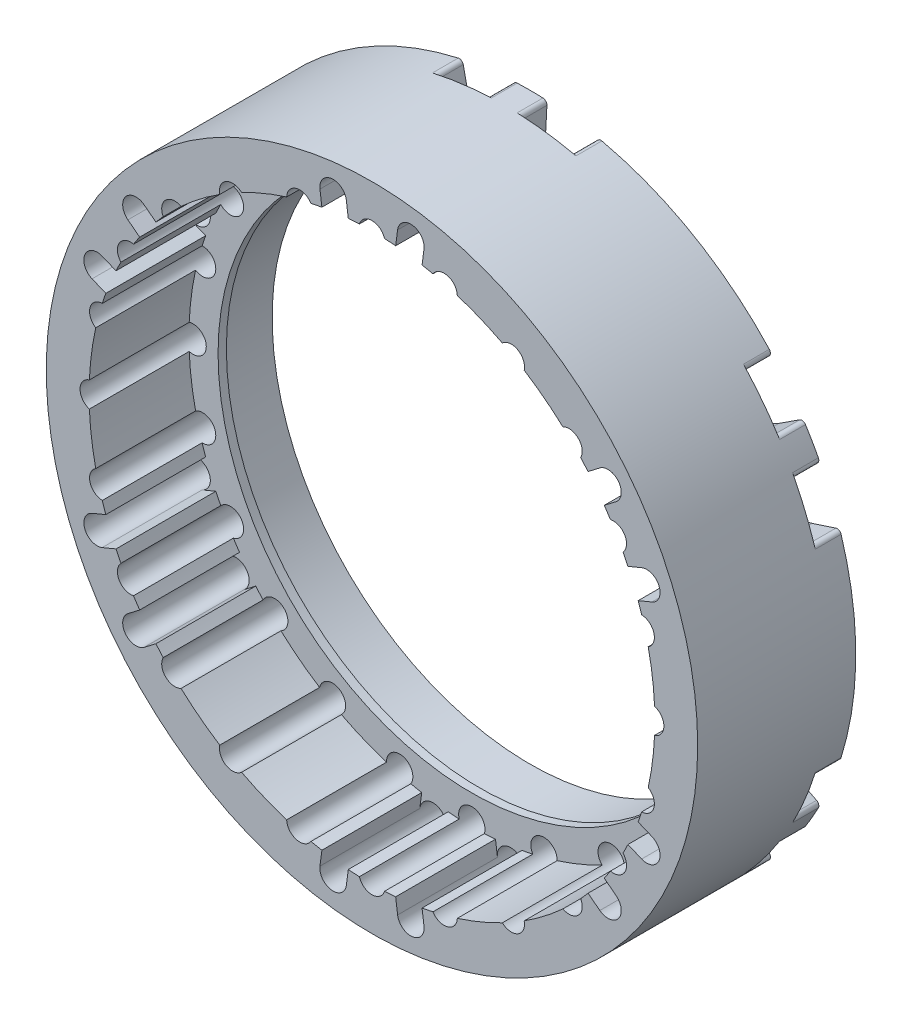
SolidWorks part; units mm, degrees
material "ABS"
ref_plane "Front Plane" through (0, 0, 0) normal (0, 0, 1) x (1, 0, 0)
ref_plane "Top Plane" through (0, 0, 0) normal (0, 1, 0) x (1, 0, 0)
ref_plane "Right Plane" through (0, 0, 0) normal (1, 0, 0) x (0, 0, -1)
sketch "CYC Master Sketch" plane through (0, 0, 0) normal (0, 0, 1) x (1, 0, 0)
  circle A0 centre (0, 0) radius 39.15
  circle A2 centre (0, 0) radius 33.5 construction
  circle A3 centre (-33.5, 0) radius 1.585
  circle A4 centre (-32.3585, 8.6704) radius 1.585
  circle A5 centre (-29.0119, 16.75) radius 1.585
  circle A6 centre (-23.6881, 23.6881) radius 1.585
  circle A7 centre (-16.75, 29.0119) radius 1.585
  circle A8 centre (-8.6704, 32.3585) radius 1.585
  circle A9 centre (0, 33.5) radius 1.585
  circle A10 centre (8.6704, 32.3585) radius 1.585
  circle A11 centre (16.75, 29.0119) radius 1.585
  circle A12 centre (23.6881, 23.6881) radius 1.585
  circle A13 centre (29.0119, 16.75) radius 1.585
  circle A14 centre (32.3585, 8.6704) radius 1.585
  circle A15 centre (33.5, 0) radius 1.585
  circle A16 centre (32.3585, -8.6704) radius 1.585
  circle A17 centre (29.0119, -16.75) radius 1.585
  circle A18 centre (23.6881, -23.6881) radius 1.585
  circle A19 centre (16.75, -29.0119) radius 1.585
  circle A20 centre (8.6704, -32.3585) radius 1.585
  circle A21 centre (0, -33.5) radius 1.585
  circle A22 centre (-8.6704, -32.3585) radius 1.585
  circle A23 centre (0, 0) radius 34
  circle A24 centre (-16.75, -29.0119) radius 1.585
  circle A25 centre (-23.6881, -23.6881) radius 1.585
  circle A26 centre (-29.0119, -16.75) radius 1.585
  circle A27 centre (-32.3585, -8.6704) radius 1.585
  circle A28 centre (0, 0) radius 31 construction
  circle A29 centre (0, 0) radius 24.975 construction
  circle A30 centre (0, 0) radius 35.75 construction
  circle A31 centre (4.6663, -35.4442) radius 1.6
  circle A32 centre (-4.6663, -35.4442) radius 1.6
  circle A33 centre (-28.3624, -21.7632) radius 1.6
  circle A34 centre (-33.0287, -13.6809) radius 1.6
  circle A35 centre (-33.0287, 13.6809) radius 1.6
  circle A36 centre (-28.3624, 21.7632) radius 1.6
  circle A37 centre (-4.6663, 35.4442) radius 1.6
  circle A38 centre (4.6663, 35.4442) radius 1.6
  circle A39 centre (28.3624, 21.7632) radius 1.6
  circle A40 centre (33.0287, 13.6809) radius 1.6
  circle A41 centre (33.0287, -13.6809) radius 1.6
  circle A42 centre (28.3624, -21.7632) radius 1.6
  point P47 (0, 0)
  point P72 (0, 0)
extrude "Gearbox Wall" add sketch "CYC Master Sketch" along normal blind 19 contours A0 A23 A13 A14 A15 A16 A17 A18 A19 A20 A21 A22 A3 A4 A5 A6 A7 A8 A9 A10 A11 A12 region at (-38.0427, 0, 0)
extrude "Gearbox Bottom" add sketch "CYC Master Sketch<3>" along normal blind 7 contours A21 A23 | A23 A20 | A20 A23 | A23 A19 | A19 A23 | A23 A18 | A18 A23 | A23 A17 | A17 A23 | A23 A16 | A16 A23 | A23 A15 | A15 A23 | A23 A14 | A14 A23 | A23 A13 | A13 A23 | A23 A12 | A12 A23 | A23 A11 | A11 A23 | A23 A10 | A10 A23 | A23 A9 | A9 A23 | A23 A8 | A8 A23 | A23 A7 | A7 A23 | A23 A6 | A6 A23 | A23 A5 | A5 A23 | A23 A4 | A4 A23 | A23 A3 | A3 A23 | A23 A22 | A22 A23 | A13 A23 A12 A11 A10 A9 A8 A7 A6 A5 A4 A3 A22 A21 A20 A19 A18 A17 A16 A15 A14 | A24 | A25 | A26 | A27 | A21 region at (-33.0823, 0, 0) region at (0, 0, 0) region at (-34.4435, 0, 0) region at (-31.9551, 8.5623, 0) region at (-33.2699, 8.9146, 0) region at (-28.6502, 16.5412, 0) region at (-29.829, 17.2218, 0) region at (-23.3928, 23.3928, 0) region at (-24.3553, 24.3553, 0) region at (-16.5412, 28.6502, 0) region at (-17.2218, 29.829, 0) region at (-8.5623, 31.9551, 0) region at (-8.9146, 33.2699, 0) region at (-8.9146, -33.2699, 0) region at (-8.5623, -31.9551, 0) region at (0, 33.0823, 0) region at (0, 34.4435, 0) region at (0, -33.0823, 0) region at (8.5623, 31.9551, 0) region at (8.9146, 33.2699, 0) region at (8.9146, -33.2699, 0) region at (8.5623, -31.9551, 0) region at (16.5412, 28.6502, 0) region at (17.2218, 29.829, 0) region at (17.2218, -29.829, 0) region at (16.5412, -28.6502, 0) region at (23.3928, 23.3928, 0) region at (24.3553, 24.3553, 0) region at (24.3553, -24.3553, 0) region at (23.3928, -23.3928, 0) region at (28.6502, 16.5412, 0) region at (29.829, 17.2218, 0) region at (29.829, -17.2218, 0) region at (28.6502, -16.5412, 0) region at (31.9551, 8.5623, 0) region at (33.2699, 8.9146, 0) region at (33.2699, -8.9146, 0) region at (31.9551, -8.5623, 0) region at (33.0823, 0, 0) region at (34.4435, 0, 0)
sketch "CYC Master Sketch<3>" plane through (0, 0, 0) normal (0, 0, 1) x (1, 0, 0) same geometry as "CYC Master Sketch"
extrude "Pin Cut" cut sketch "CYC Master Sketch<2>" against normal blind 4 from surface contours A23 A7 | A7 A23 | A23 A6 | A6 A23 | A23 A5 | A5 A23 | A23 A4 | A4 A23 | A23 A3 | A3 A23 | A23 A22 | A22 A23 | A23 A21 | A21 A23 | A23 A20 | A20 A23 | A23 A19 | A19 A23 | A23 A18 | A18 A23 | A23 A17 | A17 A23 | A16 A23 | A23 A16 | A15 A23 | A23 A15 | A23 A14 | A14 A23 | A23 A13 | A13 A23 | A23 A12 | A12 A23 | A23 A11 | A11 A23 | A10 A23 | A23 A9 | A9 A23 | A23 A8 | A8 A23 | A23 A10 | A23 A24 | A23 A24 | A23 A25 | A23 A25 | A23 A26 | A23 A26 | A23 A27 | A23 A27 region at (-33.0823, 0, 0) region at (-34.4435, 0, 0) region at (-31.9551, 8.5623, 0) region at (-33.2699, 8.9146, 0) region at (-31.9551, -8.5623, 0) region at (-33.2699, -8.9146, 0) region at (-28.6502, 16.5412, 0) region at (-29.829, 17.2218, 0) region at (-28.6502, -16.5412, 0) region at (-29.829, -17.2218, 0) region at (-23.3928, 23.3928, 0) region at (-24.3553, 24.3553, 0) region at (-23.3928, -23.3928, 0) region at (-24.3553, -24.3553, 0) region at (-16.5412, 28.6502, 0) region at (-17.2218, 29.829, 0) region at (-16.5412, -28.6502, 0) region at (-17.2218, -29.829, 0) region at (-8.5623, 31.9551, 0) region at (-8.9146, 33.2699, 0) region at (-8.9146, -33.2699, 0) region at (-8.5623, -31.9551, 0) region at (0, 33.0823, 0) region at (0, 34.4435, 0) region at (0, -34.4435, 0) region at (0, -33.0823, 0) region at (8.5623, 31.9551, 0) region at (8.9146, 33.2699, 0) region at (8.9146, -33.2699, 0) region at (8.5623, -31.9551, 0) region at (16.5412, 28.6502, 0) region at (17.2218, 29.829, 0) region at (17.2218, -29.829, 0) region at (16.5412, -28.6502, 0) region at (23.3928, 23.3928, 0) region at (24.3553, 24.3553, 0) region at (24.3553, -24.3553, 0) region at (23.3928, -23.3928, 0) region at (28.6502, 16.5412, 0) region at (29.829, 17.2218, 0) region at (29.829, -17.2218, 0) region at (28.6502, -16.5412, 0) region at (31.9551, 8.5623, 0) region at (33.2699, 8.9146, 0) region at (33.2699, -8.9146, 0) region at (31.9551, -8.5623, 0) region at (33.0823, 0, 0) region at (34.4435, 0, 0) starting at face at (0, 0, 7)
sketch "CYC Master Sketch<2>" plane through (0, 0, 0) normal (0, 0, 1) x (1, 0, 0) same geometry as "CYC Master Sketch"
sketch "CYC Master" plane through (0, 0, 7) normal (0, 0, 1) x (1, 0, 0)
  circle A0 centre (0, 0) radius 39.15
  circle A2 centre (0, 0) radius 33.5 construction
  circle A3 centre (-33.5, 0) radius 1.585
  circle A4 centre (-32.3585, 8.6704) radius 1.585
  circle A5 centre (-29.0119, 16.75) radius 1.585
  circle A6 centre (-23.6881, 23.6881) radius 1.585
  circle A7 centre (-16.75, 29.0119) radius 1.585
  circle A8 centre (-8.6704, 32.3585) radius 1.585
  circle A9 centre (0, 33.5) radius 1.585
  circle A10 centre (8.6704, 32.3585) radius 1.585
  circle A11 centre (16.75, 29.0119) radius 1.585
  circle A12 centre (23.6881, 23.6881) radius 1.585
  circle A13 centre (29.0119, 16.75) radius 1.585
  circle A14 centre (32.3585, 8.6704) radius 1.585
  circle A15 centre (33.5, 0) radius 1.585
  circle A16 centre (32.3585, -8.6704) radius 1.585
  circle A17 centre (29.0119, -16.75) radius 1.585
  circle A18 centre (23.6881, -23.6881) radius 1.585
  circle A19 centre (16.75, -29.0119) radius 1.585
  circle A20 centre (8.6704, -32.3585) radius 1.585
  circle A21 centre (0, -33.5) radius 1.585
  circle A22 centre (-8.6704, -32.3585) radius 1.585
  circle A23 centre (0, 0) radius 34
  circle A24 centre (-16.75, -29.0119) radius 1.585
  circle A25 centre (-23.6881, -23.6881) radius 1.585
  circle A26 centre (-29.0119, -16.75) radius 1.585
  circle A27 centre (-32.3585, -8.6704) radius 1.585
  circle A28 centre (0, 0) radius 31 construction
  circle A29 centre (0, 0) radius 24.975 construction
  circle A30 centre (0, 0) radius 35.75 construction
  circle A31 centre (4.6663, -35.4442) radius 1.6
  circle A32 centre (-4.6663, -35.4442) radius 1.6
  circle A33 centre (-28.3624, -21.7632) radius 1.6
  circle A34 centre (-33.0287, -13.6809) radius 1.6
  circle A35 centre (-33.0287, 13.6809) radius 1.6
  circle A36 centre (-28.3624, 21.7632) radius 1.6
  circle A37 centre (-4.6663, 35.4442) radius 1.6
  circle A38 centre (4.6663, 35.4442) radius 1.6
  circle A39 centre (28.3624, 21.7632) radius 1.6
  circle A40 centre (33.0287, 13.6809) radius 1.6
  circle A41 centre (33.0287, -13.6809) radius 1.6
  circle A42 centre (28.3624, -21.7632) radius 1.6
  point P47 (0, 0)
  point P72 (0, 0)
sketch "Sketch2" plane through (0, 0, 7) normal (0, 0, 1) x (1, 0, 0)
  circle A0 centre (0, 0) radius 31
  circle A1 centre (0, 0) radius 31 construction
extrude "Housing Bearing Cut" cut sketch "Sketch2" against normal through all
sketch "Sketch3" plane through (0, 0, 7) normal (0, 0, 1) x (1, 0, 0)
  circle A0 centre (0, 0) radius 31
  circle A1 centre (0, 0) radius 30.5
  circle A2 centre (0, 0) radius 31 construction
  dimension "D1" = 61
  dimension "Housing Bearing Outer (Driven)" = 62
extrude "Housing Bearing Retainer" add sketch "Sketch3" against normal blind 0.5
sketch "Sketch5" plane through (0, 0, 0) normal (0, 0, -1) x (-1, 0, 0)
  line L0 (0, 0) -> (31.7579, 16.1759) construction
  line L1 (0, 0) -> (33.8943, 11.0181) construction
  line L2 (33.8943, 11.0181) -> (37.2322, 12.1031)
  line L3 (31.7579, 16.1759) -> (34.8854, 17.7689)
  line L4 (0, 0) -> (33.9049, 19.575) construction
  line L5 (26.4891, 23.8443) -> (29.0977, 26.1925)
  line L6 (29.8877, 19.4152) -> (32.831, 21.3271)
  line L7 (33.8943, -11.0181) -> (37.2322, -12.1031)
  line L8 (31.7579, -16.1759) -> (34.8854, -17.7689)
  line L9 (26.4891, -23.8443) -> (29.0977, -26.1925)
  line L10 (29.8877, -19.4152) -> (32.831, -21.3271)
  line L11 (7.4052, -34.8624) -> (8.1345, -38.2956)
  line L12 (1.8702, -35.5911) -> (2.0543, -39.0961)
  line L13 (-7.4052, -34.8624) -> (-8.1345, -38.2956)
  line L14 (-1.8702, -35.5911) -> (-2.0543, -39.0961)
  line L15 (-26.4891, -23.8443) -> (-29.0977, -26.1925)
  line L16 (-29.8877, -19.4152) -> (-32.831, -21.3271)
  line L17 (-33.8943, -11.0181) -> (-37.2322, -12.1031)
  line L18 (-31.7579, -16.1759) -> (-34.8854, -17.7689)
  line L19 (-33.8943, 11.0181) -> (-37.2322, 12.1031)
  line L20 (-31.7579, 16.1759) -> (-34.8854, 17.7689)
  line L21 (-26.4891, 23.8443) -> (-29.0977, 26.1925)
  line L22 (-29.8877, 19.4152) -> (-32.831, 21.3271)
  line L23 (-7.4052, 34.8624) -> (-8.1345, 38.2956)
  line L24 (-1.8702, 35.5911) -> (-2.0543, 39.0961)
  line L25 (7.4052, 34.8624) -> (8.1345, 38.2956)
  line L26 (1.8702, 35.5911) -> (2.0543, 39.0961)
  arc A0 (31.7579, 16.1759) -> (33.8943, 11.0181) centre (33.0287, 13.6809) ccw
  arc A1 (-32.831, -21.3271) -> (-29.0977, -26.1925) centre (0, 0) ccw
  circle A2 centre (0, 0) radius 39.15 construction
  arc A3 (34.8854, 17.7689) -> (37.2322, 12.1031) centre (0, 0) cw
  arc A4 (32.831, 21.3271) -> (29.0977, 26.1925) centre (0, 0) ccw
  arc A5 (29.8877, 19.4152) -> (26.4891, 23.8443) centre (28.3624, 21.7632) cw
  arc A6 (34.8854, -17.7689) -> (37.2322, -12.1031) centre (0, 0) ccw
  arc A7 (31.7579, -16.1759) -> (33.8943, -11.0181) centre (33.0287, -13.6809) cw
  arc A8 (32.831, -21.3271) -> (29.0977, -26.1925) centre (0, 0) cw
  arc A9 (29.8877, -19.4152) -> (26.4891, -23.8443) centre (28.3624, -21.7632) ccw
  arc A10 (2.0543, -39.0961) -> (8.1345, -38.2956) centre (0, 0) ccw
  arc A11 (1.8702, -35.5911) -> (7.4052, -34.8624) centre (4.6663, -35.4442) cw
  arc A12 (-2.0543, -39.0961) -> (-8.1345, -38.2956) centre (0, 0) cw
  arc A13 (-1.8702, -35.5911) -> (-7.4052, -34.8624) centre (-4.6663, -35.4442) ccw
  arc A14 (-29.8877, -19.4152) -> (-26.4891, -23.8443) centre (-28.3624, -21.7632) cw
  arc A15 (-34.8854, -17.7689) -> (-37.2322, -12.1031) centre (0, 0) cw
  arc A16 (-31.7579, -16.1759) -> (-33.8943, -11.0181) centre (-33.0287, -13.6809) ccw
  arc A17 (-34.8854, 17.7689) -> (-37.2322, 12.1031) centre (0, 0) ccw
  arc A18 (-31.7579, 16.1759) -> (-33.8943, 11.0181) centre (-33.0287, 13.6809) cw
  arc A19 (-32.831, 21.3271) -> (-29.0977, 26.1925) centre (0, 0) cw
  arc A20 (-29.8877, 19.4152) -> (-26.4891, 23.8443) centre (-28.3624, 21.7632) ccw
  arc A21 (-2.0543, 39.0961) -> (-8.1345, 38.2956) centre (0, 0) ccw
  arc A22 (-1.8702, 35.5911) -> (-7.4052, 34.8624) centre (-4.6663, 35.4442) cw
  arc A23 (2.0543, 39.0961) -> (8.1345, 38.2956) centre (0, 0) cw
  arc A24 (1.8702, 35.5911) -> (7.4052, 34.8624) centre (4.6663, 35.4442) ccw
  point P39 (0, 0)
  dimension "D1" = 5.6
  dimension "D3" = 6
  dimension "D2" = 7.5
extrude "M3 Socket Head Cutout" cut sketch "Sketch5" against normal blind 3.1
fillet "Fillet1" radius 0.5 24 edges at (-8.1345, -38.2956, 1.55) (-2.0543, -39.0961, 1.55) (2.0543, -39.0961, 1.55) (8.1345, -38.2956, 1.55) (-29.0977, -26.1925, 1.55) (-32.831, -21.3271, 1.55) (-37.2322, -12.1031, 1.55) (-34.8854, -17.7689, 1.55) (-29.0977, 26.1925, 1.55) (-32.831, 21.3271, 1.55) (-34.8854, 17.7689, 1.55) (-37.2322, 12.1031, 1.55) (-8.1345, 38.2956, 1.55) (-2.0543, 39.0961, 1.55) (8.1345, 38.2956, 1.55) (2.0543, 39.0961, 1.55) (29.0977, 26.1925, 1.55) (32.831, 21.3271, 1.55) (34.8854, 17.7689, 1.55) (37.2322, 12.1031, 1.55) (37.2322, -12.1031, 1.55) (34.8854, -17.7689, 1.55) (32.831, -21.3271, 1.55) (29.0977, -26.1925, 1.55)
sketch "Sketch6" plane through (0, 0, 19) normal (0, 0, 1) x (1, 0, 0)
  line L0 (-6.0193, 33.4629) -> (-6.2526, 35.2353)
  line L1 (-2.8467, 33.8806) -> (-3.08, 35.653)
  line L2 (0, 0) -> (-4.6663, 35.4442) construction
  line L3 (-6.0193, 33.4629) -> (-2.8467, 33.8806)
  line L4 (2.8467, 33.8806) -> (3.08, 35.653)
  line L5 (6.0193, 33.4629) -> (6.2526, 35.2353)
  line L6 (2.8467, 33.8806) -> (6.0193, 33.4629)
  line L7 (0, 0) -> (4.6663, 35.4442) construction
  line L8 (0, 0) -> (-2.8467, 33.8806) construction
  line L9 (0, 0) -> (6.0193, 33.4629) construction
  arc A0 (-1.5149, 33.9662) -> (-7.3279, 33.2009) centre (0, 0) ccw construction
  circle A1 centre (-4.6663, 35.4442) radius 1.6 construction
  arc A2 (-3.08, 35.653) -> (-6.2526, 35.2353) centre (-4.6663, 35.4442) ccw
  arc A3 (6.2526, 35.2353) -> (3.08, 35.653) centre (4.6663, 35.4442) ccw
  dimension "D1" = 2
  dimension "D2" = 15
  dimension "D3" = 34
extrude "Cut-Extrude1" cut sketch "Sketch6" against normal up to surface (12 mm away) contours A2 L0 L3 L1 | L4 A3 L5 L6 up to face at (0, 0, 7)
pattern_circular "CirPattern1" count 6 over 360 about axis through (0, 0, 0) along (0, 0, 1) of "Cut-Extrude1", "Housing Bearing Cut"
sketch "Sketch7" plane through (0, 0, 7) normal (0, 0, 1) x (1, 0, 0)
  circle A0 centre (0, 0) radius 31
  circle A1 centre (0, 0) radius 31 construction
  circle A2 centre (0, 0) radius 30.5
  dimension "D1" = 61
extrude "Boss-Extrude1" add sketch "Sketch7" against normal blind 1
